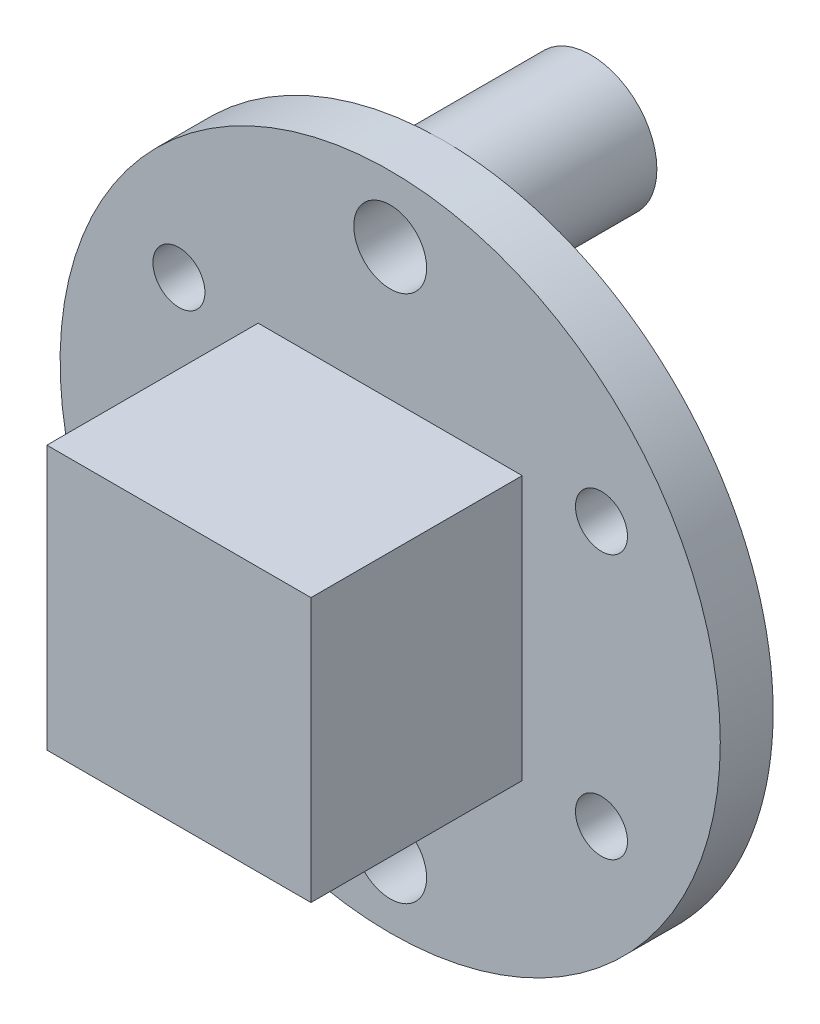
SolidWorks part; units mm, degrees
material "PLA"
ref_plane "Front Plane" through (0, 0, 0) normal (0, 0, 1) x (1, 0, 0)
ref_plane "Top Plane" through (0, 0, 0) normal (0, 1, 0) x (1, 0, 0)
ref_plane "Right Plane" through (0, 0, 0) normal (1, 0, 0) x (0, 0, -1)
sketch "Sketch1" plane through (0, 0, 0) normal (0, 0, 1) x (1, 0, 0)
  line L0 (0, 0) -> (5.8527, 0) construction
  line L1 (0, 0) -> (0, 4.6978) construction
  circle A0 centre (0, 0) radius 15.875
  circle A1 centre (0, 12.7) radius 1.75
  circle A2 centre (0, 12.7) radius 3.175
  circle A3 centre (0, -12.7) radius 1.75
  circle A4 centre (0, -12.7) radius 3.175
  circle A5 centre (-10.16, 6.35) radius 1.25
  circle A6 centre (10.16, 6.35) radius 1.25
  circle A7 centre (10.16, -6.35) radius 1.25
  circle A8 centre (-10.16, -6.35) radius 1.25
  dimension "D1" = 31.75
  dimension "D2" = 3.5
  dimension "D4" = 2.5
  dimension "D3" = 12.7
  dimension "D5" = 12.7
  dimension "D6" = 20.32
extrude "Boss-Extrude1" add sketch "Sketch1" along normal blind 2.54 contours A0 A4 A2 A6 A5 A7 A8 | A2 A1 | A4 A3 region at (2.1816, 14.8816, 0) region at (-2.1816, -10.5184, 0) region at (0, 0, 0)
extrude "Boss-Extrude2" add sketch "Sketch1<3>" against normal blind 7.11 contours A2 A1 | A4 A3 region at (2.1816, 14.8816, 0) region at (-2.1816, -10.5184, 0)
sketch "Sketch1<3>" plane through (0, 0, 0) normal (0, 0, 1) x (1, 0, 0) same geometry as "Sketch1"
sketch "Sketch2" plane through (0, 0, 2.54) normal (0, 0, 1) x (1, 0, 0)
  line L1 (-6.35, -6.35) -> (6.35, -6.35)
  line L2 (-6.35, -6.35) -> (-6.35, 6.35)
  line L3 (-6.35, 6.35) -> (6.35, 6.35)
  line L4 (6.35, -6.35) -> (6.35, 6.35)
  line L5 (-6.35, -6.35) -> (6.35, 6.35) construction
  line L6 (-6.35, 6.35) -> (6.35, -6.35) construction
  circle A1 centre (0, 0) radius 15.875
  circle A2 centre (0, 0) radius 15.875
  dimension "D2" = 12.7
  dimension "D1" = 0
extrude "Boss-Extrude3" add sketch "Sketch2" along normal blind 10.16 contours L1 L4 L3 L2 region at (0, 0, 2.54)
